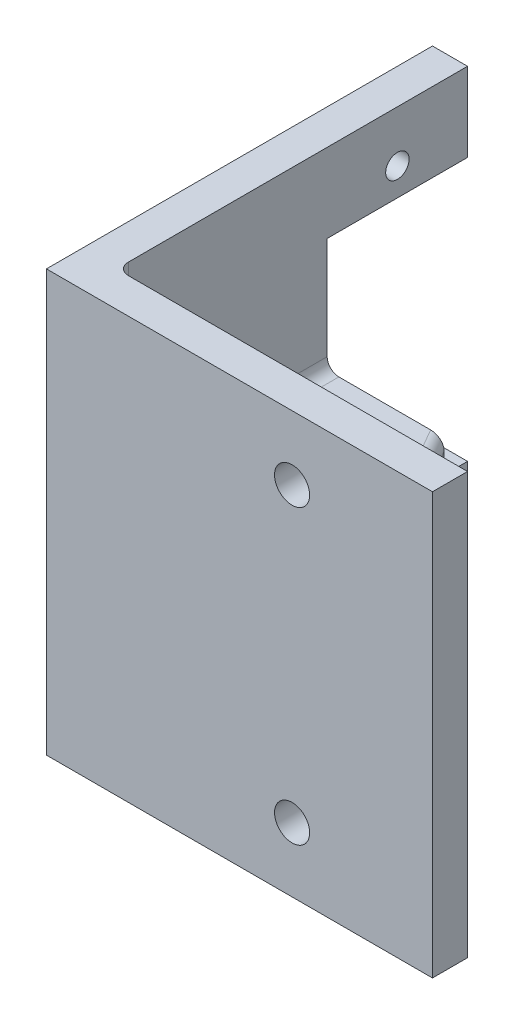
SolidWorks part; units mm, degrees
ref_plane "Front Plane" through (0, 0, 0) normal (0, 0, 1) x (1, 0, 0)
ref_plane "Top Plane" through (0, 0, 0) normal (0, 1, 0) x (1, 0, 0)
ref_plane "Right Plane" through (0, 0, 0) normal (1, 0, 0) x (0, 0, -1)
sketch "Sketch1" plane through (0, 0, 0) normal (0, 1, 0) x (1, 0, 0)
  line L0 (0, 30) -> (0, 0)
  line L1 (0, 0) -> (30, 0)
  dimension "D1" = 30
extrude "Extrude-Thin1" add sketch "Sketch1" along normal mid plane 36 thin thin type one direction wall 3
sketch "Sketch2" plane through (0, 0, 0) normal (1, 0, 0) x (0, 0, -1)
  line L0 (-4.3404, 0) -> (30.9328, 0) construction
  line L1 (30, 11.25) -> (18, 11.25)
  line L2 (30, 11.25) -> (30, -11.25)
  line L3 (30, -11.25) -> (18, -11.25)
  line L4 (18, 11.25) -> (18, -11.25)
  line L5 (30, 11.25) -> (18, -11.25) construction
  line L6 (30, -11.25) -> (18, 11.25) construction
  line L8 (30, 18) -> (30, -18) construction
  line L9 (24, 22.9117) -> (24, -24.2701) construction
  circle A0 centre (24, -13.625) radius 1
  circle A1 centre (24, 13.625) radius 1
  point P0 (24, 0)
  dimension "D3" = 2
  dimension "D1" = 22.5
  dimension "D2" = 12
  dimension "D4" = 27.25
extrude "Cut-Extrude1" cut sketch "Sketch2" against normal through all
sketch "Sketch3" plane through (0, 0, 0) normal (0, 1, 0) x (1, 0, 0)
  line L2 (0, 18) -> (10, 18)
  line L3 (10, 18) -> (20.3923, 0)
  line L4 (20.3923, 0) -> (0, 0)
  line L5 (0, 0) -> (0, 18)
  point P0 (11.5061, 19.761)
  dimension "D1" = 18
  dimension "D2" = 120
  dimension "D3" = 10
extrude "Boss-Extrude1" add sketch "Sketch3" along normal mid plane 3
sketch "Sketch4" plane through (0, 0, 0) normal (0, 0, -1) x (-1, 0, 0)
  line L0 (3.7517, 0) -> (-31.4762, 0) construction
  line L1 (-30, 18) -> (-30, -18) construction
  circle A0 centre (-18, 12.5) radius 1.5
  circle A1 centre (-18, -12.5) radius 1.5
  point P7 (0, 0)
  point P8 (0, 0)
  point P9 (-21.5599, 11.32)
  point P10 (0, 0)
  point P11 (0, 0)
  point P12 (0, 0)
  dimension "D2" = 3
  dimension "D1" = 25
  dimension "D3" = 12
extrude "Cut-Extrude2" cut sketch "Sketch4" against normal through all
fillet "Fillet1" radius 1 9 edges at (10.1962, 1.5, 0) (20.3923, 0, 0) (10.1962, -1.5, 0) (0, 1.5, -9) (0, -1.5, -9) (0, 9.75, 0) (0, -9.75, 0) (15.1962, -1.5, -9) (15.1962, 1.5, -9)
